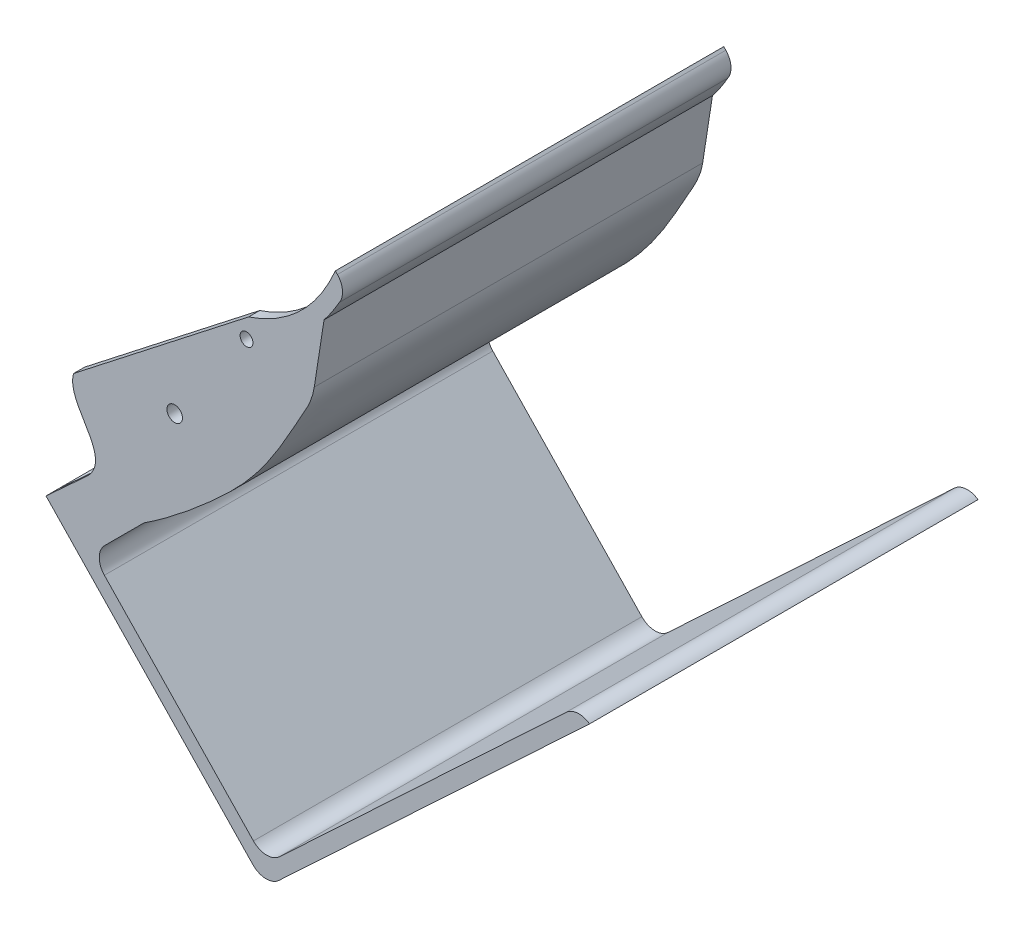
SolidWorks part; units mm, degrees
ref_plane "Front Plane" through (0, 0, 0) normal (0, 0, 1) x (1, 0, 0)
ref_plane "Top Plane" through (0, 0, 0) normal (0, 1, 0) x (1, 0, 0)
ref_plane "Right Plane" through (0, 0, 0) normal (1, 0, 0) x (0, 0, -1)
ref_plane "Plane1" through (0, 30, 0) normal (0, 1, 0) x (1, 0, 0)
sketch "Sketch8" plane through (0, 0, 0) normal (0, 0, 1) x (1, 0, 0)
  line L4 (194.8486, 149.6688) -> (147.4998, 112.7374)
  line L6 (150.8706, 90.2873) -> (140.0516, 80.3531)
  circle A1 centre (174.8358, 117.0002) radius 2.1
  circle A2 centre (194.2587, 144.1419) radius 1.74
  spline S0 degree 3 poles (140.0516, 80.3531) (155.5927, 83.4482) (173.0988, 95.918) (191.4145, 112.9772) (199.579, 124.4916) (204.7781, 134.1712) (209.3517, 141.9906) (208.0101, 153.2753) (198.0182, 148.5628) (194.8486, 149.6688) knots 0 0 0 0 0.401406 0.551774 0.650467 0.768454 0.835895 0.892032 1 1 1 1
  spline S1 degree 3 poles (147.4998, 112.7374) (145.2656, 104.8355) (158.9324, 97.556) (150.8706, 90.2873) knots 0 0 0 0 1 1 1 1
  point P1 (138.8596, 81.4404)
  point P2 (138.8596, 81.4404)
  point P4 (140.0327, 80.3951)
  point P5 (139.7288, 80.7657)
  point P9 (140.0516, 80.3531)
extrude "Boss-Extrude5" add sketch "Sketch8" along normal blind 3
sketch "Sketch18" plane through (0, 0, 0) normal (0, 0, 1) x (1, 0, 0)
  line L0 (140.0516, 80.3531) -> (199.3949, 18.4271)
  line L4 (218.2785, 172.1595) -> (286.997, 100.4504)
  line L11 (199.3949, 18.4271) -> (286.997, 100.4504)
  spline S1 degree 2 poles (194.8486, 149.6688) (210.9116, 155.0393) (218.2785, 172.1595) knots 0 0 0 1 1 1
  spline S2 degree 3 poles (-857.5026, 1806.3534) (-38.523, 12.1826) (104.1633, 31.712) (191.4145, 112.9772) (199.579, 124.4916) (204.7781, 134.1712) (209.3517, 141.9906) (204.8309, 180.0177) (30.1156, -25.0575) (1370.9259, 1766.8671) knots -2.448188 -2.448188 -2.448188 -2.448188 0.401406 0.551774 0.650467 0.768454 0.835895 0.892032 1.548717 1.548717 1.548717 1.548717 only from (140.0516, 80.3531) to (194.8486, 149.6688)
  spline S3 degree 3 poles (140.0516, 80.3531) (155.5927, 83.4482) (173.0988, 95.918) (191.4145, 112.9772) (199.579, 124.4916) (204.7781, 134.1712) (209.3517, 141.9906) (208.0101, 153.2753) (198.0182, 148.5628) (194.8486, 149.6688) knots 0 0 0 0 0.401406 0.551774 0.650467 0.768454 0.835895 0.892032 1 1 1 1
  dimension "D3" = 120
  dimension "D1" = 0
extrude "Boss-Extrude6" add sketch "Sketch18" against normal blind 102 and the other way blind 3
sketch "Sketch28" plane through (0, 0, -102) normal (0, 0, -1) x (-1, 0, 0)
  line L0 (-208.618, 142.6957) -> (-211.4291, 160.851)
  parabola Q0 (-218.2785, 172.1595) -> (-194.8486, 149.6688) focus (-194.6882, 169.2923) apex (-205.2456, 155.0277) construction
  parabola Q3 (-218.2785, 172.1595) -> (-194.8486, 149.6688) focus (-194.6882, 169.2923) apex (-205.2456, 155.0277)
  parabola Q4 (-211.4291, 160.851) -> (-194.8486, 149.6688) focus (-194.6882, 169.2923) apex (-205.2456, 155.0277)
  spline S0 degree 3 poles (-140.0516, 80.3531) (-155.5927, 83.4482) (-173.0988, 95.918) (-191.4145, 112.9772) (-199.579, 124.4916) (-204.7781, 134.1712) (-209.3517, 141.9906) (-208.0101, 153.2753) (-198.0182, 148.5628) (-194.8486, 149.6688) knots 0 0 0 0 0.401406 0.551774 0.650467 0.768454 0.835895 0.892032 1 1 1 1 construction
  spline S4 degree 3 poles (-1370.9531, 1766.9035) (-30.1134, -25.0601) (-204.8308, 180.018) (-209.3517, 141.9906) (-204.7781, 134.1712) (-199.579, 124.4916) (-191.4145, 112.9772) (-104.1628, 31.7115) (38.5248, 12.1824) (857.5184, 1806.3882) knots -0.548722 -0.548722 -0.548722 -0.548722 0.107968 0.164105 0.231546 0.349533 0.448226 0.598594 3.448206 3.448206 3.448206 3.448206 only from (-194.8486, 149.6688) to (-140.0516, 80.3531)
  spline S5 degree 3 poles (-194.8486, 149.6688) (-198.0182, 148.5628) (-208.0101, 153.2753) (-208.9733, 145.1732) (-208.6314, 142.7828) (-208.618, 142.6957) knots 0 0 0 0 0.107968 0.164105 0.166243 0.166243 0.166243 0.166243
  dimension "D2" = 0
extrude "Cut-Extrude6" cut sketch "Sketch28" against normal blind 102
sketch "Sketch29" plane through (0, 0, -102) normal (0, 0, -1) x (-1, 0, 0)
  line L0 (-219.332, 165.2789) -> (-221.693, 168.5964)
  line L1 (-286.997, 100.4504) -> (-218.2785, 172.1595) construction
  line L2 (-221.693, 168.5964) -> (-284.2292, 103.3386)
  line L3 (-281.3092, 100.6045) -> (-284.2292, 103.3386)
  line L4 (-166.5668, 87.3148) -> (-152.4454, 73.2012)
  line L12 (-212.5709, 142.0836) -> (-215.215, 159.1598)
  line L13 (-219.332, 165.2789) -> (-281.3092, 100.6045)
  line L14 (-281.3092, 100.6045) -> (-199.5473, 24.0494)
  line L15 (-199.5473, 24.0494) -> (-147.6649, 78.1898)
  line L16 (-212.5709, 142.0836) -> (-215.215, 159.1598)
  line L18 (-281.3092, 100.6045) -> (-199.5473, 24.0494)
  line L19 (-199.5473, 24.0494) -> (-152.4454, 73.2012)
  spline S3 degree 3 poles (1568.1972, 1054.5349) (-1978.1885, -1087.1326) (1519.7497, 1510.7871) (-2036.4394, -637.4764) knots -34.260454 -34.260454 -34.260454 -34.260454 48.230269 48.230269 48.230269 48.230269 only from (-215.215, 159.1598) to (-219.332, 165.2789)
  spline S4 degree 3 poles (1016.256, 1697.0196) (83.7999, 110.2112) (-79.0475, 27.7948) (-169.4082, 89.2127) (-170.2155, 89.7774) (-171.8137, 90.9247) (-172.6052, 91.5076) (-174.9589, 93.2809) (-176.5008, 94.4961) (-179.5421, 96.9775) (-181.0417, 98.2437) (-184.0104, 100.8126) (-185.4801, 102.1147) (-188.3665, 104.783) (-189.7853, 106.1516) (-192.5218, 108.9561) (-193.8416, 110.394) (-197.6177, 114.8424) (-199.8856, 117.9912) (-204.0643, 124.5513) (-205.9655, 127.9696) (-208.352, 132.2352) (-208.8302, 133.0878) (-209.7957, 134.7892) (-210.2776, 135.6402) (-211.1487, 137.384) (-211.5385, 138.2765) (-225.4015, 178.7562) (-106.7354, 277.8313) (1556.6071, 1072.3057) knots -3.193284 -3.193284 -3.193284 -3.193284 0.25 0.25 0.28125 0.28125 0.3125 0.3125 0.375 0.375 0.4375 0.4375 0.5 0.5 0.5625 0.5625 0.625 0.625 0.75 0.75 0.875 0.875 0.90625 0.90625 0.9375 0.9375 0.96875 0.96875 2.304583 2.304583 2.304583 2.304583 only from (-147.6649, 78.1898) to (-212.5709, 142.0836)
  spline S5 degree 3 poles (-215.215, 159.1598) (-216.7537, 161.0876) (-218.1176, 163.1329) (-219.332, 165.2789) knots 0 0 0 0 1 1 1 1
  spline S6 degree 3 poles (-166.5668, 87.3148) (-167.2474, 87.7549) (-167.9235, 88.2036) (-169.4082, 89.2127) (-170.2155, 89.7774) (-171.8137, 90.9247) (-172.6052, 91.5076) (-174.9589, 93.2809) (-176.5008, 94.4961) (-179.5421, 96.9775) (-181.0417, 98.2437) (-184.0104, 100.8126) (-185.4801, 102.1147) (-188.3665, 104.783) (-189.7853, 106.1516) (-192.5218, 108.9561) (-193.8416, 110.394) (-197.6177, 114.8424) (-199.8856, 117.9912) (-204.0643, 124.5513) (-205.9655, 127.9696) (-208.352, 132.2352) (-208.8302, 133.0878) (-209.7957, 134.7892) (-210.2776, 135.6402) (-211.1487, 137.384) (-211.5385, 138.2765) (-212.1723, 140.1271) (-212.4168, 141.085) (-212.5709, 142.0836) knots 0.22416 0.22416 0.22416 0.22416 0.25 0.25 0.28125 0.28125 0.3125 0.3125 0.375 0.375 0.4375 0.4375 0.5 0.5 0.5625 0.5625 0.625 0.625 0.75 0.75 0.875 0.875 0.90625 0.90625 0.9375 0.9375 0.96875 0.96875 1 1 1 1
  dimension "D1" = 4
extrude "Cut-Extrude7" cut sketch "Sketch29" against normal through all
fillet "Fillet4" radius 5 6 edges at (211.4291, 160.851, -51) (199.3949, 18.4271, -49.5) (221.693, 168.5964, -49.5) (284.2292, 103.3386, -49.5) (199.5473, 24.0494, -49.5) (152.4454, 73.2012, -49.5)
